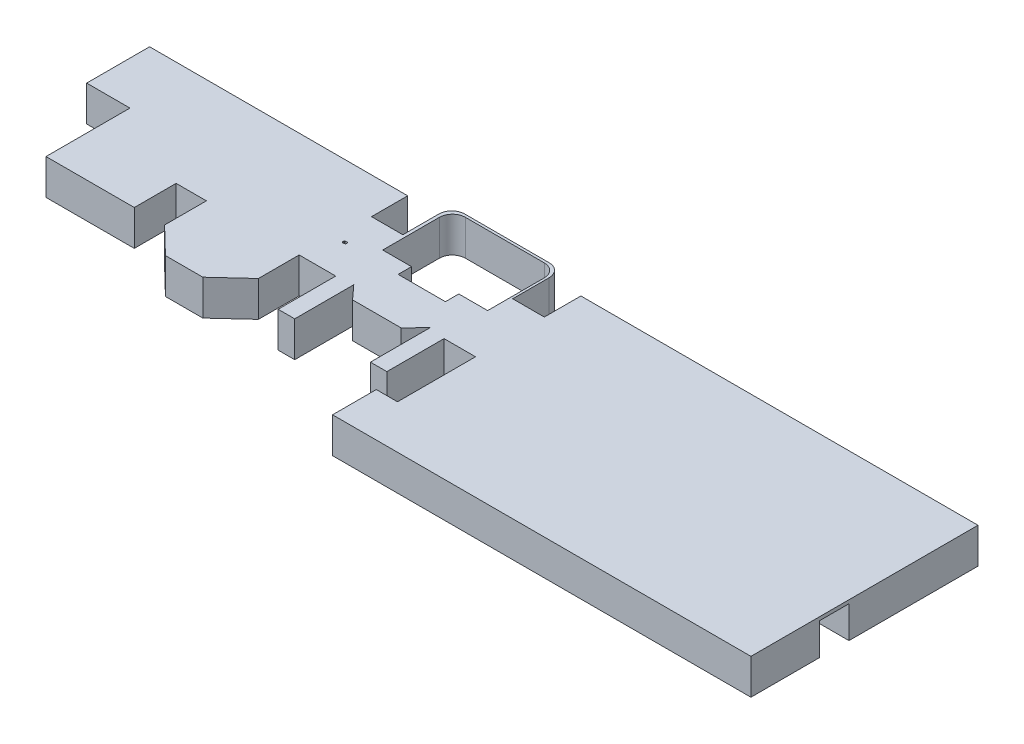
SolidWorks part; units mm, degrees
ref_plane "Front" through (0, 0, 0) normal (0, 0, 1) x (1, 0, 0)
ref_plane "Top" through (0, 0, 0) normal (0, 1, 0) x (1, 0, 0)
ref_plane "Right" through (0, 0, 0) normal (1, 0, 0) x (0, 0, -1)
sketch "Sketch1" plane through (0, 0, 0) normal (0, 1, 0) x (1, 0, 0)
  line L0 (-95852.0448, 1004.5028) -> (-93652.0448, 1004.5028) construction
  line L1 (-92722.4429, 3032.5434) -> (-92722.4429, -4248.038)
  line L2 (-92722.4429, -4248.038) -> (-87714.6303, -4248.038)
  line L3 (-87714.6303, -13961.4489) -> (-77497.684, -13961.4489)
  line L4 (-77497.684, -13961.4489) -> (-77497.684, -9120.8318)
  line L5 (-77497.684, -9120.8318) -> (-73993.9992, -9120.8318)
  line L6 (-73993.9992, -9120.8318) -> (-73993.9992, -13961.4489)
  line L7 (-73993.9992, -13961.4489) -> (-70874.3536, -16978.2439)
  line L8 (-70874.3536, -16978.2439) -> (-66551.4365, -16978.2439)
  line L9 (-66551.4365, -16978.2439) -> (-63204.0372, -13893.8222)
  line L10 (-63204.0372, -13893.8222) -> (-63204.0372, -9177.5359)
  line L11 (-63204.0372, -9177.5359) -> (-58974.2106, -9177.5359)
  line L12 (-58974.2106, -9177.5359) -> (-58974.2106, -15834.789)
  line L13 (-58974.2106, -15834.789) -> (-57060.4997, -15834.789)
  line L14 (-57060.4997, -15834.789) -> (-57060.4997, -8999.6581)
  line L15 (-57060.4997, -8999.6581) -> (-55614.7024, -10587.319)
  line L16 (-55614.7024, -10587.319) -> (-49997.8266, -10587.319)
  line L17 (-49997.8266, -10587.319) -> (-48338.774, -8876.9988)
  line L18 (-48338.774, -8876.9988) -> (-48338.774, -15794.4358)
  line L19 (-48338.774, -15794.4358) -> (-46437.4412, -15794.4358)
  line L20 (-46437.4412, -15794.4358) -> (-46437.4412, -9177.5359)
  line L21 (-46437.4412, -9177.5359) -> (-42795.907, -9177.5359)
  line L22 (-42795.907, -9177.5359) -> (-42795.907, -18201.9351)
  line L23 (-42795.907, -18201.9351) -> (-45253.4333, -18201.9351)
  line L24 (-45253.4333, -18201.9351) -> (-45253.4333, -23262.6588)
  line L25 (-45253.4333, -23262.6588) -> (3158.9575, -23262.6588)
  line L26 (3158.9575, -23262.6588) -> (3158.9575, 3013.36)
  line L27 (3158.9575, 3013.36) -> (-42795.907, 3013.36)
  line L28 (-42795.907, 3013.36) -> (-42795.907, -1217.3234)
  line L29 (-42795.907, -1217.3234) -> (-44543.9492, -1217.3234)
  line L30 (-44543.9492, -1217.3234) -> (-44543.9492, -1414.4498)
  line L31 (-44543.9492, -1414.4498) -> (-42795.907, -1414.4498)
  line L32 (-42795.907, -1414.4498) -> (-42795.907, -5614.4796)
  line L33 (-42795.907, -5614.4796) -> (-15610.0343, -5614.4796)
  line L34 (-15610.0343, -5614.4796) -> (-15610.0343, -1822.8901)
  line L35 (-15610.0343, -1822.8901) -> (-2613.5, -1822.8901)
  line L36 (-2613.5, -1822.8901) -> (-2613.5, 969.6477)
  line L37 (-2613.5, 969.6477) -> (-646.0273, 969.6477)
  line L38 (-646.0273, 969.6477) -> (-646.0273, -9455.9367)
  line L39 (-646.0273, -9455.9367) -> (-2613.5, -9455.9367)
  line L40 (-2613.5, -9455.9367) -> (-2613.5, -5114.7195)
  line L41 (-2613.5, -5114.7195) -> (-12313.0283, -5114.7195)
  line L42 (-12313.0283, -5114.7195) -> (-12313.0283, -11916.6398)
  line L43 (-12313.0283, -11916.6398) -> (3158.9575, -11916.6398)
  line L44 (-62020.0141, -5163.6876) -> (-62020.0141, -5388.889)
  line L45 (-62020.0141, -5388.889) -> (-61911.5095, -5388.889)
  line L46 (-61911.5095, -5388.889) -> (-61911.5095, -5437.5424)
  line L47 (-61911.5095, -5437.5424) -> (-61719.1755, -5437.5424)
  line L48 (-61719.1755, -5437.5424) -> (-61719.1755, -5388.889)
  line L49 (-61719.1755, -5388.889) -> (-61612.0786, -5388.889)
  line L50 (-61612.0786, -5388.889) -> (-61612.0786, -5163.6876)
  line L52 (-61970.0141, -5113.6876) -> (-61662.0786, -5113.6876)
  line L54 (-55960.8823, -4121.4792) -> (-55960.8823, -5665.3674)
  line L55 (-55960.8823, -5665.3674) -> (-49725.6524, -5665.3674)
  line L56 (-49725.6524, -5665.3674) -> (-49725.6524, -4121.4792)
  line L57 (-49725.6524, -4121.4792) -> (-46460.002, -4121.4792)
  line L58 (-46460.002, -4121.4792) -> (-46460.002, 2994.9561)
  line L59 (-47960.002, 4494.9561) -> (-57726.5326, 4494.9561)
  line L60 (-55960.8823, -4121.4792) -> (-59226.5326, -4121.4792)
  line L61 (-59226.5326, -4121.4792) -> (-59226.5326, 2994.9561)
  line L62 (3158.9575, -15328.6011) -> (-37892.4286, -15328.6011)
  line L63 (-37892.4286, -15328.6011) -> (-37892.4286, -18201.9351)
  line L64 (-37892.4286, -18201.9351) -> (-35343.2964, -18201.9351)
  line L65 (-35343.2964, -18201.9351) -> (-35343.2964, -20101.0171)
  line L66 (-35343.2964, -20101.0171) -> (-40314.0738, -20101.0171)
  line L67 (-40314.0738, -20101.0171) -> (-40314.0738, -14936.1956)
  line L68 (-40314.0738, -14936.1956) -> (-42544.3056, -14936.1956)
  line L69 (-42544.3056, -14936.1956) -> (-42544.3056, -13384.4604)
  line L70 (-42544.3056, -13384.4604) -> (-40314.0738, -13384.4604)
  line L71 (-40314.0738, -13384.4604) -> (-40314.0738, -8605.2168)
  line L72 (-50136.471, -10373.3274) -> (-48338.774, -8619.2363)
  line L73 (-48338.774, -8619.2363) -> (-40314.0738, -8605.2168)
  line L76 (-50136.471, -10373.3274) -> (-55355.7793, -10373.3274)
  line L77 (-55355.7793, -10373.3274) -> (-57060.4997, -8626.2285)
  line L78 (-57060.4997, -8626.2285) -> (-63481.1822, -8626.2285)
  line L79 (-63481.1822, -8626.2285) -> (-63481.1822, -13591.9685)
  line L80 (-63481.1822, -13591.9685) -> (-66551.4365, -16662.2229)
  line L81 (-66551.4365, -16662.2229) -> (-70681.0433, -16662.2229)
  line L82 (-70681.0433, -16662.2229) -> (-73704.5204, -13701.7349)
  line L83 (-73704.5204, -13701.7349) -> (-73704.5204, -5657.4342)
  line L84 (-73704.5204, -5657.4342) -> (-69334.0401, -5657.4342)
  line L85 (-69334.0401, -5657.4342) -> (-69334.0401, -2723.9748)
  line L86 (-69334.0401, -2723.9748) -> (-77712.6536, -2723.9748)
  line L87 (-77712.6536, -2723.9748) -> (-77712.6536, -3732.5162)
  line L88 (-87714.6303, -4248.038) -> (-87714.6303, -13961.4489)
  line L89 (-92722.4429, 3032.5434) -> (-62854.9695, 3032.5434)
  line L91 (-62893.6785, -5660.1107) -> (-66861.7243, -5660.1107)
  line L92 (-66861.7243, -5660.1107) -> (-66861.7243, -2698.1933)
  line L93 (-66861.7243, -2698.1933) -> (-65946.0214, -2698.1933)
  line L94 (-65946.0214, -2698.1933) -> (-65946.0214, -1043.5021)
  line L95 (-65946.0214, -1043.5021) -> (-87423.7151, -1043.5021)
  line L96 (-87423.7151, -1043.5021) -> (-87423.7151, -8904.221)
  line L97 (-87423.7151, -8904.221) -> (-84329.7257, -8904.221)
  line L98 (-84329.7257, -8904.221) -> (-84329.7257, -10733.514)
  line L99 (-84329.7257, -10733.514) -> (-82681.1037, -10733.514)
  line L100 (-82681.1037, -10733.514) -> (-82681.1037, -2716.2423)
  line L101 (-82681.1037, -2716.2423) -> (-79338.6918, -2716.2423)
  line L102 (-77712.6536, -3732.5162) -> (-79338.6918, -3732.5162)
  line L103 (-79338.6918, -3732.5162) -> (-79338.6918, -2716.2423)
  line L104 (-62854.9695, 3032.5434) -> (-62854.9695, -1153.6152)
  line L105 (-62854.9695, -1153.6152) -> (-61139.275, -1153.6152)
  line L106 (-61139.275, -1153.6152) -> (-61139.275, -1541.516)
  line L107 (-61139.275, -1541.516) -> (-62893.6785, -1541.516)
  line L108 (-62893.6785, -1541.516) -> (-62893.6785, -5660.1107)
  arc A0 (-62020.0141, -5163.6876) -> (-61970.0141, -5113.6876) centre (-61970.0141, -5163.6876) cw
  arc A1 (-61662.0786, -5113.6876) -> (-61612.0786, -5163.6876) centre (-61662.0786, -5163.6876) cw
  arc A2 (-59226.5326, 2994.9561) -> (-57726.5326, 4494.9561) centre (-57726.5326, 2994.9561) cw
  arc A3 (-46460.002, 2994.9561) -> (-47960.002, 4494.9561) centre (-47960.002, 2994.9561) ccw
  dimension "D1" = 50
  dimension "D2" = 50
  dimension "D3" = 1500
  dimension "D4" = 1500
sketch "Sketch5" plane through (0, 0, 0) normal (0, 1, 0) x (1, 0, 0)
  line L0 (-95852.0448, 1004.5028) -> (-93652.0448, 1004.5028) construction
  line L1 (-92722.4429, 3032.5434) -> (-92722.4429, -4248.038)
  line L2 (-92722.4429, -4248.038) -> (-87714.6303, -4248.038)
  line L3 (-87714.6303, -13961.4489) -> (-77497.684, -13961.4489)
  line L4 (-77497.684, -13961.4489) -> (-77497.684, -9120.8318)
  line L5 (-77497.684, -9120.8318) -> (-73993.9992, -9120.8318)
  line L6 (-73993.9992, -9120.8318) -> (-73993.9992, -13961.4489)
  line L7 (-73993.9992, -13961.4489) -> (-70874.3536, -16978.2439)
  line L8 (-70874.3536, -16978.2439) -> (-66551.4365, -16978.2439)
  line L9 (-66551.4365, -16978.2439) -> (-63204.0372, -13893.8222)
  line L10 (-63204.0372, -13893.8222) -> (-63204.0372, -9177.5359)
  line L11 (-63204.0372, -9177.5359) -> (-58974.2106, -9177.5359)
  line L12 (-58974.2106, -9177.5359) -> (-58974.2106, -15834.789)
  line L13 (-58974.2106, -15834.789) -> (-57060.4997, -15834.789)
  line L14 (-57060.4997, -15834.789) -> (-57060.4997, -8999.6581)
  line L15 (-57060.4997, -8999.6581) -> (-55614.7024, -10587.319)
  line L16 (-55614.7024, -10587.319) -> (-49997.8266, -10587.319)
  line L17 (-49997.8266, -10587.319) -> (-48338.774, -8876.9988)
  line L18 (-48338.774, -8876.9988) -> (-48338.774, -15794.4358)
  line L19 (-48338.774, -15794.4358) -> (-46437.4412, -15794.4358)
  line L20 (-46437.4412, -15794.4358) -> (-46437.4412, -9177.5359)
  line L21 (-46437.4412, -9177.5359) -> (-42795.907, -9177.5359)
  line L22 (-42795.907, -9177.5359) -> (-42795.907, -18201.9351)
  line L23 (-42795.907, -18201.9351) -> (-45253.4333, -18201.9351)
  line L24 (-45253.4333, -18201.9351) -> (-45253.4333, -23262.6588)
  line L25 (-45253.4333, -23262.6588) -> (3158.9575, -23262.6588)
  line L26 (3158.9575, -23262.6588) -> (3158.9575, 3013.36)
  line L27 (3158.9575, 3013.36) -> (-42795.907, 3013.36)
  line L28 (-42795.907, 3013.36) -> (-42795.907, -1217.3234)
  line L29 (-42795.907, -1217.3234) -> (-44543.9492, -1217.3234)
  line L30 (-44543.9492, -1217.3234) -> (-44543.9492, -1414.4498)
  line L31 (-44543.9492, -1414.4498) -> (-42795.907, -1414.4498)
  line L32 (-42795.907, -1414.4498) -> (-42795.907, -5614.4796)
  line L33 (-42795.907, -5614.4796) -> (-15610.0343, -5614.4796)
  line L34 (-15610.0343, -5614.4796) -> (-15610.0343, -1822.8901)
  line L35 (-15610.0343, -1822.8901) -> (-2613.5, -1822.8901)
  line L36 (-2613.5, -1822.8901) -> (-2613.5, 969.6477)
  line L37 (-2613.5, 969.6477) -> (-646.0273, 969.6477)
  line L38 (-646.0273, 969.6477) -> (-646.0273, -9455.9367)
  line L39 (-646.0273, -9455.9367) -> (-2613.5, -9455.9367)
  line L40 (-2613.5, -9455.9367) -> (-2613.5, -5114.7195)
  line L41 (-2613.5, -5114.7195) -> (-12313.0283, -5114.7195)
  line L42 (-12313.0283, -5114.7195) -> (-12313.0283, -11916.6398)
  line L43 (-12313.0283, -11916.6398) -> (3158.9575, -11916.6398)
  line L44 (-62020.0141, -5163.6876) -> (-62020.0141, -5388.889)
  line L45 (-62020.0141, -5388.889) -> (-61911.5095, -5388.889)
  line L46 (-61911.5095, -5388.889) -> (-61911.5095, -5437.5424)
  line L47 (-61911.5095, -5437.5424) -> (-61719.1755, -5437.5424)
  line L48 (-61719.1755, -5437.5424) -> (-61719.1755, -5388.889)
  line L49 (-61719.1755, -5388.889) -> (-61612.0786, -5388.889)
  line L50 (-61612.0786, -5388.889) -> (-61612.0786, -5163.6876)
  line L52 (-61970.0141, -5113.6876) -> (-61662.0786, -5113.6876)
  line L54 (-55960.8823, -4121.4792) -> (-55960.8823, -5665.3674)
  line L55 (-55960.8823, -5665.3674) -> (-49725.6524, -5665.3674)
  line L56 (-49725.6524, -5665.3674) -> (-49725.6524, -4121.4792)
  line L57 (-49725.6524, -4121.4792) -> (-46460.002, -4121.4792)
  line L58 (-46460.002, -4121.4792) -> (-46460.002, 3008.3496)
  line L59 (-47960.002, 4508.3496) -> (-57726.5326, 4508.3496)
  line L60 (-55960.8823, -4121.4792) -> (-59226.5326, -4121.4792)
  line L61 (-59226.5326, -4121.4792) -> (-59226.5326, 3008.3496)
  line L62 (3158.9575, -15328.6011) -> (-37892.4286, -15328.6011)
  line L63 (-37892.4286, -15328.6011) -> (-37892.4286, -18201.9351)
  line L64 (-37892.4286, -18201.9351) -> (-35343.2964, -18201.9351)
  line L65 (-35343.2964, -18201.9351) -> (-35343.2964, -20101.0171)
  line L66 (-35343.2964, -20101.0171) -> (-40314.0738, -20101.0171)
  line L67 (-40314.0738, -20101.0171) -> (-40314.0738, -14936.1956)
  line L68 (-40314.0738, -14936.1956) -> (-42544.3056, -14936.1956)
  line L69 (-42544.3056, -14936.1956) -> (-42544.3056, -13384.4604)
  line L70 (-42544.3056, -13384.4604) -> (-40314.0738, -13384.4604)
  line L71 (-40314.0738, -13384.4604) -> (-40314.0738, -8605.2168)
  line L72 (-50136.471, -10373.3274) -> (-48338.774, -8619.2363)
  line L73 (-48338.774, -8619.2363) -> (-40314.0738, -8605.2168)
  line L76 (-50136.471, -10373.3274) -> (-55355.7793, -10373.3274)
  line L77 (-55355.7793, -10373.3274) -> (-57060.4997, -8626.2285)
  line L78 (-57060.4997, -8626.2285) -> (-63481.1822, -8626.2285)
  line L79 (-63481.1822, -8626.2285) -> (-63481.1822, -13591.9685)
  line L80 (-63481.1822, -13591.9685) -> (-66551.4365, -16662.2229)
  line L81 (-66551.4365, -16662.2229) -> (-70681.0433, -16662.2229)
  line L82 (-70681.0433, -16662.2229) -> (-73704.5204, -13701.7349)
  line L83 (-73704.5204, -13701.7349) -> (-73704.5204, -5657.4342)
  line L84 (-73704.5204, -5657.4342) -> (-69334.0401, -5657.4342)
  line L85 (-69334.0401, -5657.4342) -> (-69334.0401, -2723.9748)
  line L86 (-69334.0401, -2723.9748) -> (-77712.6536, -2723.9748)
  line L87 (-77712.6536, -2723.9748) -> (-77712.6536, -3732.5162)
  line L88 (-87714.6303, -4248.038) -> (-87714.6303, -13961.4489)
  line L89 (-92722.4429, 3032.5434) -> (-62854.9695, 3032.5434)
  line L91 (-62893.6785, -5660.1107) -> (-66861.7243, -5660.1107)
  line L92 (-66861.7243, -5660.1107) -> (-66861.7243, -2698.1933)
  line L93 (-66861.7243, -2698.1933) -> (-65946.0214, -2698.1933)
  line L94 (-65946.0214, -2698.1933) -> (-65946.0214, -1043.5021)
  line L95 (-65946.0214, -1043.5021) -> (-87423.7151, -1043.5021)
  line L96 (-87423.7151, -1043.5021) -> (-87423.7151, -8904.221)
  line L97 (-87423.7151, -8904.221) -> (-84329.7257, -8904.221)
  line L98 (-84329.7257, -8904.221) -> (-84329.7257, -10733.514)
  line L99 (-84329.7257, -10733.514) -> (-82681.1037, -10733.514)
  line L100 (-82681.1037, -10733.514) -> (-82681.1037, -2716.2423)
  line L101 (-82681.1037, -2716.2423) -> (-79338.6918, -2716.2423)
  line L102 (-77712.6536, -3732.5162) -> (-79338.6918, -3732.5162)
  line L103 (-79338.6918, -3732.5162) -> (-79338.6918, -2716.2423)
  line L104 (-62854.9695, 3032.5434) -> (-62854.9695, -1153.6152)
  line L105 (-62854.9695, -1153.6152) -> (-61139.275, -1153.6152)
  line L106 (-61139.275, -1153.6152) -> (-61139.275, -1541.516)
  line L107 (-61139.275, -1541.516) -> (-62893.6785, -1541.516)
  line L108 (-62893.6785, -1541.516) -> (-62893.6785, -5660.1107)
  line L109 (-48224.7261, 4213.7819) -> (-57364.0184, 4213.7819)
  line L110 (-55530.7517, -5398.4292) -> (-50057.9928, -5398.4292)
  line L111 (-46724.7261, -3848.0726) -> (-46724.7261, 2713.7819)
  line L112 (-55530.7517, -3848.0726) -> (-55530.7517, -5398.4292)
  line L113 (-58864.0184, -3848.0726) -> (-58864.0184, 2713.7819)
  line L114 (-50057.9928, -5398.4292) -> (-50057.9928, -3848.0726)
  line L115 (-50057.9928, -3848.0726) -> (-46724.7261, -3848.0726)
  line L116 (-55530.7517, -3848.0726) -> (-58864.0184, -3848.0726)
  arc A0 (-62020.0141, -5163.6876) -> (-61970.0141, -5113.6876) centre (-61970.0141, -5163.6876) cw
  arc A1 (-61662.0786, -5113.6876) -> (-61612.0786, -5163.6876) centre (-61662.0786, -5163.6876) cw
  arc A2 (-59226.5326, 3008.3496) -> (-57726.5326, 4508.3496) centre (-57726.5326, 3008.3496) cw
  arc A3 (-46460.002, 3008.3496) -> (-47960.002, 4508.3496) centre (-47960.002, 3008.3496) ccw
  arc A4 (-58864.0184, 2713.7819) -> (-57364.0184, 4213.7819) centre (-57364.0184, 2713.7819) cw
  arc A5 (-46724.7261, 2713.7819) -> (-48224.7261, 4213.7819) centre (-48224.7261, 2713.7819) ccw
  dimension "D1" = 50
  dimension "D2" = 50
  dimension "D3" = 1500
  dimension "D4" = 1500
  dimension "D5" = 1500
  dimension "D6" = 1500
extrude "Boss-Extrude1" add sketch "Sketch5" along normal blind 4100 contours L108 L107 L106 L105 L104 L89 L1 L2 L88 L3 L4 L5 L6 L7 L8 L9 L10 L11 L12 L13 L14 L15 L16 L17 L18 L19 L20 L21 L22 L23 L24 L25 L26 L62 L63 L64 L65 L66 L67 L68 L69 L70 L71 L73 L72 L76 L77 L78 L79 L80 L81 | L42 L43 L26 L27 L28 L29 L30 L31 L32 L33 L34 L35 L36 L37 L38 L39 L40 L41 | L58 A3 L59 A2 L61 L60 L54 L55 L56 L57 region at (-77788.7062, 0, -2038.3261) region at (-18334.7077, 0, 2623.5134) region at (-57593.7074, 0, 3958.2344)
ref_plane "Plane1" through (0, 0, -3022.9517) normal (0, 0, -1) x (-1, 0, 0)
sketch "Sketch8" plane through (0, 0, -3022.9517) normal (0, 0, -1) x (-1, 0, 0)
  line L0 (3231.2525, 3102.6563) -> (7231.2525, 3102.6563)
  line L1 (-2028.4059, 3102.6563) -> (1971.5941, 3102.6563)
  line L2 (-2028.4059, 3102.6563) -> (-2028.4059, 1527.9311)
  line L3 (-2028.4059, 1527.9311) -> (1971.5941, 1527.9311)
  line L4 (1971.5941, 3102.6563) -> (1971.5941, 1527.9311)
  line L9 (3231.2525, 1527.9311) -> (7231.2525, 1527.9311)
  line L10 (7231.2525, 3102.6563) -> (7231.2525, 1527.9311)
  line L11 (3231.2525, 3102.6563) -> (3231.2525, 1527.9311)
  line L12 (17815.6364, 3102.6563) -> (17815.6364, 1527.9311)
  line L13 (8555.978, 3102.6563) -> (12555.978, 3102.6563)
  line L14 (13815.6364, 3102.6563) -> (13815.6364, 1527.9311)
  line L15 (13815.6364, 1527.9311) -> (17815.6364, 1527.9311)
  line L16 (13815.6364, 3102.6563) -> (17815.6364, 3102.6563)
  line L17 (8555.978, 3102.6563) -> (8555.978, 1527.9311)
  line L18 (8555.978, 1527.9311) -> (12555.978, 1527.9311)
  line L19 (12555.978, 3102.6563) -> (12555.978, 1527.9311)
  line L20 (25763.8862, 3102.6563) -> (25763.8862, 1527.9311)
  line L21 (21763.8862, 3102.6563) -> (21763.8862, 1527.9311)
  line L22 (21763.8862, 1527.9311) -> (25763.8862, 1527.9311)
  line L23 (41607.9286, 3102.6563) -> (41607.9286, 1527.9311)
  line L24 (27023.5446, 1527.9311) -> (31023.5446, 1527.9311)
  line L25 (21763.8862, 3102.6563) -> (25763.8862, 3102.6563)
  line L26 (37607.9286, 1527.9311) -> (41607.9286, 1527.9311)
  line L27 (32348.2702, 1527.9311) -> (36348.2702, 1527.9311)
  line L28 (27023.5446, 3102.6563) -> (27023.5446, 1527.9311)
  line L29 (37607.9286, 3102.6563) -> (41607.9286, 3102.6563)
  line L30 (31023.5446, 3102.6563) -> (31023.5446, 1527.9311)
  line L31 (32348.2702, 3102.6563) -> (32348.2702, 1527.9311)
  line L32 (36348.2702, 3102.6563) -> (36348.2702, 1527.9311)
  line L33 (37607.9286, 3102.6563) -> (37607.9286, 1527.9311)
  line L34 (27023.5446, 3102.6563) -> (31023.5446, 3102.6563)
  line L35 (32348.2702, 3102.6563) -> (36348.2702, 3102.6563)
  line L36 (70871.2704, 3102.6563) -> (74871.2704, 3102.6563)
  line L37 (81455.6543, 1527.9311) -> (85455.6543, 1527.9311)
  line L38 (90715.3127, 3102.6563) -> (90715.3127, 1527.9311)
  line L39 (85455.6543, 3102.6563) -> (85455.6543, 1527.9311)
  line L40 (70871.2704, 3102.6563) -> (70871.2704, 1527.9311)
  line L41 (76130.9288, 3102.6563) -> (76130.9288, 1527.9311)
  line L42 (86715.3127, 3102.6563) -> (86715.3127, 1527.9311)
  line L43 (80130.9288, 3102.6563) -> (80130.9288, 1527.9311)
  line L44 (86715.3127, 1527.9311) -> (90715.3127, 1527.9311)
  line L45 (86715.3127, 3102.6563) -> (90715.3127, 3102.6563)
  line L46 (76130.9288, 1527.9311) -> (80130.9288, 1527.9311)
  line L47 (76130.9288, 3102.6563) -> (80130.9288, 3102.6563)
  line L48 (70871.2704, 1527.9311) -> (74871.2704, 1527.9311)
  line L49 (81455.6543, 3102.6563) -> (81455.6543, 1527.9311)
  line L50 (74871.2704, 3102.6563) -> (74871.2704, 1527.9311)
  line L51 (81455.6543, 3102.6563) -> (85455.6543, 3102.6563)
  line L52 (65598.8585, 3102.6563) -> (69598.8585, 3102.6563)
  line L53 (69598.8585, 3102.6563) -> (69598.8585, 1527.9311)
  line L54 (65598.8585, 1527.9311) -> (69598.8585, 1527.9311)
  line L55 (65598.8585, 3102.6563) -> (65598.8585, 1527.9311)
sketch "Sketch10" plane through (0, 0, -3022.9517) normal (0, 0, -1) x (-1, 0, 0)
  line L0 (3231.2525, 3102.6563) -> (7231.2525, 3102.6563)
  line L1 (-2028.4059, 3102.6563) -> (1971.5941, 3102.6563)
  line L2 (-2028.4059, 3102.6563) -> (-2028.4059, 1527.9311)
  line L3 (-2028.4059, 1527.9311) -> (1971.5941, 1527.9311)
  line L4 (1971.5941, 3102.6563) -> (1971.5941, 1527.9311)
  line L9 (3231.2525, 1527.9311) -> (7231.2525, 1527.9311)
  line L10 (7231.2525, 3102.6563) -> (7231.2525, 1527.9311)
  line L11 (3231.2525, 3102.6563) -> (3231.2525, 1527.9311)
  line L12 (17815.6364, 3102.6563) -> (17815.6364, 1527.9311)
  line L13 (8555.978, 3102.6563) -> (12555.978, 3102.6563)
  line L14 (13815.6364, 3102.6563) -> (13815.6364, 1527.9311)
  line L15 (13815.6364, 1527.9311) -> (17815.6364, 1527.9311)
  line L16 (13815.6364, 3102.6563) -> (17815.6364, 3102.6563)
  line L17 (8555.978, 3102.6563) -> (8555.978, 1527.9311)
  line L18 (8555.978, 1527.9311) -> (12555.978, 1527.9311)
  line L19 (12555.978, 3102.6563) -> (12555.978, 1527.9311)
  line L20 (25763.8862, 3102.6563) -> (25763.8862, 1527.9311)
  line L21 (21763.8862, 3102.6563) -> (21763.8862, 1527.9311)
  line L22 (21763.8862, 1527.9311) -> (25763.8862, 1527.9311)
  line L23 (41607.9286, 3102.6563) -> (41607.9286, 1527.9311)
  line L24 (27023.5446, 1527.9311) -> (31023.5446, 1527.9311)
  line L25 (21763.8862, 3102.6563) -> (25763.8862, 3102.6563)
  line L26 (37607.9286, 1527.9311) -> (41607.9286, 1527.9311)
  line L27 (32348.2702, 1527.9311) -> (36348.2702, 1527.9311)
  line L28 (27023.5446, 3102.6563) -> (27023.5446, 1527.9311)
  line L29 (37607.9286, 3102.6563) -> (41607.9286, 3102.6563)
  line L30 (31023.5446, 3102.6563) -> (31023.5446, 1527.9311)
  line L31 (32348.2702, 3102.6563) -> (32348.2702, 1527.9311)
  line L32 (36348.2702, 3102.6563) -> (36348.2702, 1527.9311)
  line L33 (37607.9286, 3102.6563) -> (37607.9286, 1527.9311)
  line L34 (27023.5446, 3102.6563) -> (31023.5446, 3102.6563)
  line L35 (32348.2702, 3102.6563) -> (36348.2702, 3102.6563)
  line L36 (70871.2704, 3102.6563) -> (74871.2704, 3102.6563)
  line L37 (81455.6543, 1527.9311) -> (85455.6543, 1527.9311)
  line L38 (90715.3127, 3102.6563) -> (90715.3127, 1527.9311)
  line L39 (85455.6543, 3102.6563) -> (85455.6543, 1527.9311)
  line L40 (70871.2704, 3102.6563) -> (70871.2704, 1527.9311)
  line L41 (76130.9288, 3102.6563) -> (76130.9288, 1527.9311)
  line L42 (86715.3127, 3102.6563) -> (86715.3127, 1527.9311)
  line L43 (80130.9288, 3102.6563) -> (80130.9288, 1527.9311)
  line L44 (86715.3127, 1527.9311) -> (90715.3127, 1527.9311)
  line L45 (86715.3127, 3102.6563) -> (90715.3127, 3102.6563)
  line L46 (76130.9288, 1527.9311) -> (80130.9288, 1527.9311)
  line L47 (76130.9288, 3102.6563) -> (80130.9288, 3102.6563)
  line L48 (70871.2704, 1527.9311) -> (74871.2704, 1527.9311)
  line L49 (81455.6543, 3102.6563) -> (81455.6543, 1527.9311)
  line L50 (74871.2704, 3102.6563) -> (74871.2704, 1527.9311)
  line L51 (81455.6543, 3102.6563) -> (85455.6543, 3102.6563)
  line L52 (65598.8585, 3102.6563) -> (69598.8585, 3102.6563)
  line L53 (69598.8585, 3102.6563) -> (69598.8585, 1527.9311)
  line L54 (65598.8585, 1527.9311) -> (69598.8585, 1527.9311)
  line L55 (65598.8585, 3102.6563) -> (65598.8585, 1527.9311)
extrude "Cut-Extrude2" cut sketch "Sketch8" against normal blind 1000 and the other way blind 100
ref_plane "Plane2" through (0, 4100, 0) normal (0, 1, 0) x (1, 0, 0)
sketch "Sketch11" plane through (0, 4100, 0) normal (0, 1, 0) x (1, 0, 0)
  line L0 (-95852.0448, 1004.5028) -> (-93652.0448, 1004.5028) construction
  line L1 (-92722.4429, 3032.5434) -> (-92722.4429, -4248.038)
  line L2 (-92722.4429, -4248.038) -> (-87714.6303, -4248.038)
  line L3 (-87714.6303, -13961.4489) -> (-77497.684, -13961.4489)
  line L4 (-77497.684, -13961.4489) -> (-77497.684, -9120.8318)
  line L5 (-77497.684, -9120.8318) -> (-73993.9992, -9120.8318)
  line L6 (-73993.9992, -9120.8318) -> (-73993.9992, -13961.4489)
  line L7 (-73993.9992, -13961.4489) -> (-70874.3536, -16978.2439)
  line L8 (-70874.3536, -16978.2439) -> (-66551.4365, -16978.2439)
  line L9 (-66551.4365, -16978.2439) -> (-63204.0372, -13893.8222)
  line L10 (-63204.0372, -13893.8222) -> (-63204.0372, -9177.5359)
  line L11 (-63204.0372, -9177.5359) -> (-58974.2106, -9177.5359)
  line L12 (-58974.2106, -9177.5359) -> (-58974.2106, -15834.789)
  line L13 (-58974.2106, -15834.789) -> (-57060.4997, -15834.789)
  line L14 (-57060.4997, -15834.789) -> (-57060.4997, -8999.6581)
  line L15 (-57060.4997, -8999.6581) -> (-55614.7024, -10587.319)
  line L16 (-55614.7024, -10587.319) -> (-49997.8266, -10587.319)
  line L17 (-49997.8266, -10587.319) -> (-48338.774, -8876.9988)
  line L18 (-48338.774, -8876.9988) -> (-48338.774, -15794.4358)
  line L19 (-48338.774, -15794.4358) -> (-46437.4412, -15794.4358)
  line L20 (-46437.4412, -15794.4358) -> (-46437.4412, -9177.5359)
  line L21 (-46437.4412, -9177.5359) -> (-42795.907, -9177.5359)
  line L22 (-42795.907, -9177.5359) -> (-42795.907, -18201.9351)
  line L23 (-42795.907, -18201.9351) -> (-45253.4333, -18201.9351)
  line L24 (-45253.4333, -18201.9351) -> (-45253.4333, -23262.6588)
  line L25 (-45253.4333, -23262.6588) -> (3158.9575, -23262.6588)
  line L26 (3158.9575, -23262.6588) -> (3158.9575, 3013.36)
  line L27 (3158.9575, 3013.36) -> (-42795.907, 3013.36)
  line L28 (-42795.907, 3013.36) -> (-42795.907, -1217.3234)
  line L29 (-42795.907, -1217.3234) -> (-44543.9492, -1217.3234)
  line L30 (-44543.9492, -1217.3234) -> (-44543.9492, -1414.4498)
  line L31 (-44543.9492, -1414.4498) -> (-42795.907, -1414.4498)
  line L32 (-42795.907, -1414.4498) -> (-42795.907, -5614.4796)
  line L33 (-42795.907, -5614.4796) -> (-15610.0343, -5614.4796)
  line L34 (-15610.0343, -5614.4796) -> (-15610.0343, -1822.8901)
  line L35 (-15610.0343, -1822.8901) -> (-2613.5, -1822.8901)
  line L36 (-2613.5, -1822.8901) -> (-2613.5, 969.6477)
  line L37 (-2613.5, 969.6477) -> (-646.0273, 969.6477)
  line L38 (-646.0273, 969.6477) -> (-646.0273, -9455.9367)
  line L39 (-646.0273, -9455.9367) -> (-2613.5, -9455.9367)
  line L40 (-2613.5, -9455.9367) -> (-2613.5, -5114.7195)
  line L41 (-2613.5, -5114.7195) -> (-12313.0283, -5114.7195)
  line L42 (-12313.0283, -5114.7195) -> (-12313.0283, -11916.6398)
  line L43 (-12313.0283, -11916.6398) -> (3158.9575, -11916.6398)
  line L44 (-62020.0141, -5163.6876) -> (-62020.0141, -5388.889)
  line L45 (-62020.0141, -5388.889) -> (-61911.5095, -5388.889)
  line L46 (-61911.5095, -5388.889) -> (-61911.5095, -5437.5424)
  line L47 (-61911.5095, -5437.5424) -> (-61719.1755, -5437.5424)
  line L48 (-61719.1755, -5437.5424) -> (-61719.1755, -5388.889)
  line L49 (-61719.1755, -5388.889) -> (-61612.0786, -5388.889)
  line L50 (-61612.0786, -5388.889) -> (-61612.0786, -5163.6876)
  line L52 (-61970.0141, -5113.6876) -> (-61662.0786, -5113.6876)
  line L54 (-55960.8823, -4121.4792) -> (-55960.8823, -5665.3674)
  line L55 (-55960.8823, -5665.3674) -> (-49725.6524, -5665.3674)
  line L56 (-49725.6524, -5665.3674) -> (-49725.6524, -4121.4792)
  line L57 (-49725.6524, -4121.4792) -> (-46460.002, -4121.4792)
  line L58 (-46460.002, -4121.4792) -> (-46460.002, 2994.9561)
  line L59 (-47960.002, 4494.9561) -> (-57726.5326, 4494.9561)
  line L60 (-55960.8823, -4121.4792) -> (-59226.5326, -4121.4792)
  line L61 (-59226.5326, -4121.4792) -> (-59226.5326, 2994.9561)
  line L62 (3158.9575, -15328.6011) -> (-37892.4286, -15328.6011)
  line L63 (-37892.4286, -15328.6011) -> (-37892.4286, -18201.9351)
  line L64 (-37892.4286, -18201.9351) -> (-35343.2964, -18201.9351)
  line L65 (-35343.2964, -18201.9351) -> (-35343.2964, -20101.0171)
  line L66 (-35343.2964, -20101.0171) -> (-40314.0738, -20101.0171)
  line L67 (-40314.0738, -20101.0171) -> (-40314.0738, -14936.1956)
  line L68 (-40314.0738, -14936.1956) -> (-42544.3056, -14936.1956)
  line L69 (-42544.3056, -14936.1956) -> (-42544.3056, -13384.4604)
  line L70 (-42544.3056, -13384.4604) -> (-40314.0738, -13384.4604)
  line L71 (-40314.0738, -13384.4604) -> (-40314.0738, -8605.2168)
  line L72 (-50136.471, -10373.3274) -> (-48338.774, -8619.2363)
  line L73 (-48338.774, -8619.2363) -> (-40314.0738, -8605.2168)
  line L76 (-50136.471, -10373.3274) -> (-55355.7793, -10373.3274)
  line L77 (-55355.7793, -10373.3274) -> (-57060.4997, -8626.2285)
  line L78 (-57060.4997, -8626.2285) -> (-63481.1822, -8626.2285)
  line L79 (-63481.1822, -8626.2285) -> (-63481.1822, -13591.9685)
  line L80 (-63481.1822, -13591.9685) -> (-66551.4365, -16662.2229)
  line L81 (-66551.4365, -16662.2229) -> (-70681.0433, -16662.2229)
  line L82 (-70681.0433, -16662.2229) -> (-73704.5204, -13701.7349)
  line L83 (-73704.5204, -13701.7349) -> (-73704.5204, -5657.4342)
  line L84 (-73704.5204, -5657.4342) -> (-69334.0401, -5657.4342)
  line L85 (-69334.0401, -5657.4342) -> (-69334.0401, -2723.9748)
  line L86 (-69334.0401, -2723.9748) -> (-77712.6536, -2723.9748)
  line L87 (-77712.6536, -2723.9748) -> (-77712.6536, -3732.5162)
  line L88 (-87714.6303, -4248.038) -> (-87714.6303, -13961.4489)
  line L89 (-92722.4429, 3032.5434) -> (-62854.9695, 3032.5434)
  line L91 (-62893.6785, -5660.1107) -> (-66861.7243, -5660.1107)
  line L92 (-66861.7243, -5660.1107) -> (-66861.7243, -2698.1933)
  line L93 (-66861.7243, -2698.1933) -> (-65946.0214, -2698.1933)
  line L94 (-65946.0214, -2698.1933) -> (-65946.0214, -1043.5021)
  line L95 (-65946.0214, -1043.5021) -> (-87423.7151, -1043.5021)
  line L96 (-87423.7151, -1043.5021) -> (-87423.7151, -8904.221)
  line L97 (-87423.7151, -8904.221) -> (-84329.7257, -8904.221)
  line L98 (-84329.7257, -8904.221) -> (-84329.7257, -10733.514)
  line L99 (-84329.7257, -10733.514) -> (-82681.1037, -10733.514)
  line L100 (-82681.1037, -10733.514) -> (-82681.1037, -2716.2423)
  line L101 (-82681.1037, -2716.2423) -> (-79338.6918, -2716.2423)
  line L102 (-77712.6536, -3732.5162) -> (-79338.6918, -3732.5162)
  line L103 (-79338.6918, -3732.5162) -> (-79338.6918, -2716.2423)
  line L104 (-62854.9695, 3032.5434) -> (-62854.9695, -1153.6152)
  line L105 (-62854.9695, -1153.6152) -> (-61139.275, -1153.6152)
  line L106 (-61139.275, -1153.6152) -> (-61139.275, -1541.516)
  line L107 (-61139.275, -1541.516) -> (-62893.6785, -1541.516)
  line L108 (-62893.6785, -1541.516) -> (-62893.6785, -5660.1107)
  line L109 (-61139.275, -1153.6152) -> (-59226.5326, -1153.6152)
  line L110 (-44543.9492, -1217.3234) -> (-46460.002, -1217.3234)
  line L111 (-55530.7517, -3848.0726) -> (-55530.7517, -5398.4292)
  line L112 (-48204.2842, 4193.34) -> (-57384.4603, 4193.34)
  line L113 (-50057.9928, -3848.0726) -> (-46724.7261, -3848.0726)
  line L114 (-55530.7517, -5398.4292) -> (-50057.9928, -5398.4292)
  line L115 (-55530.7517, -3848.0726) -> (-58864.0184, -3848.0726)
  line L116 (-58864.0184, -3848.0726) -> (-58864.0184, 2713.7819)
  line L117 (-50057.9928, -5398.4292) -> (-50057.9928, -3848.0726)
  line L118 (-46724.7261, -3848.0726) -> (-46724.7261, 2713.7819)
  line L119 (-50057.9928, -5398.4292) -> (-50057.9928, -3848.0726) construction
  arc A0 (-62020.0141, -5163.6876) -> (-61970.0141, -5113.6876) centre (-61970.0141, -5163.6876) cw
  arc A1 (-61662.0786, -5113.6876) -> (-61612.0786, -5163.6876) centre (-61662.0786, -5163.6876) cw
  arc A2 (-59226.5326, 2994.9561) -> (-57726.5326, 4494.9561) centre (-57726.5326, 2994.9561) cw
  arc A3 (-46460.002, 2994.9561) -> (-47960.002, 4494.9561) centre (-47960.002, 2994.9561) ccw
  arc A4 (-58864.0184, 2713.7819) -> (-57384.4603, 4193.34) centre (-57384.4603, 2713.7819) cw
  arc A5 (-46724.7261, 2713.7819) -> (-48204.2842, 4193.34) centre (-48204.2842, 2713.7819) ccw
  arc A6 (-46724.7261, 2713.7819) -> (-48224.7261, 4213.7819) centre (-48224.7261, 2713.7819) ccw construction
  dimension "D1" = 50
  dimension "D2" = 50
  dimension "D3" = 1500
  dimension "D4" = 1500
extrude "Boss-Extrude2" add sketch "Sketch11" against normal blind 400 contours L108 L107 L106 L105 L104 L89 L1 L2 L88 L3 L4 L5 L6 L7 L8 L9 L10 L11 L12 L13 L14 L15 L16 L17 L18 L19 L20 L21 L22 L23 L24 L25 L26 L62 L63 L64 L65 L66 L67 L68 L69 L70 L71 L73 L72 L76 L77 L78 L79 L80 L81 | L30 L110 L58 L57 L56 L55 L54 L60 L61 L109 L106 L107 L108 L91 L92 L93 L94 L95 L96 L97 L98 L99 L100 L101 L103 L102 L87 L86 L85 L84 L83 L82 L81 L80 L79 L78 L77 L76 L72 L73 L71 L70 L69 L68 L67 L66 L65 L64 L63 L62 L26 | L42 L43 L26 L27 L28 L29 L30 L31 L32 L33 L34 L35 L36 L37 L38 L39 L40 L41 region at (-77788.7062, 4100, -2038.3261) region at (-39628.4635, 4100, 8892.387) region at (-18334.7077, 4100, 2623.5134)
extrude "Ventanas" add sketch "Sketch10" against normal blind 150
